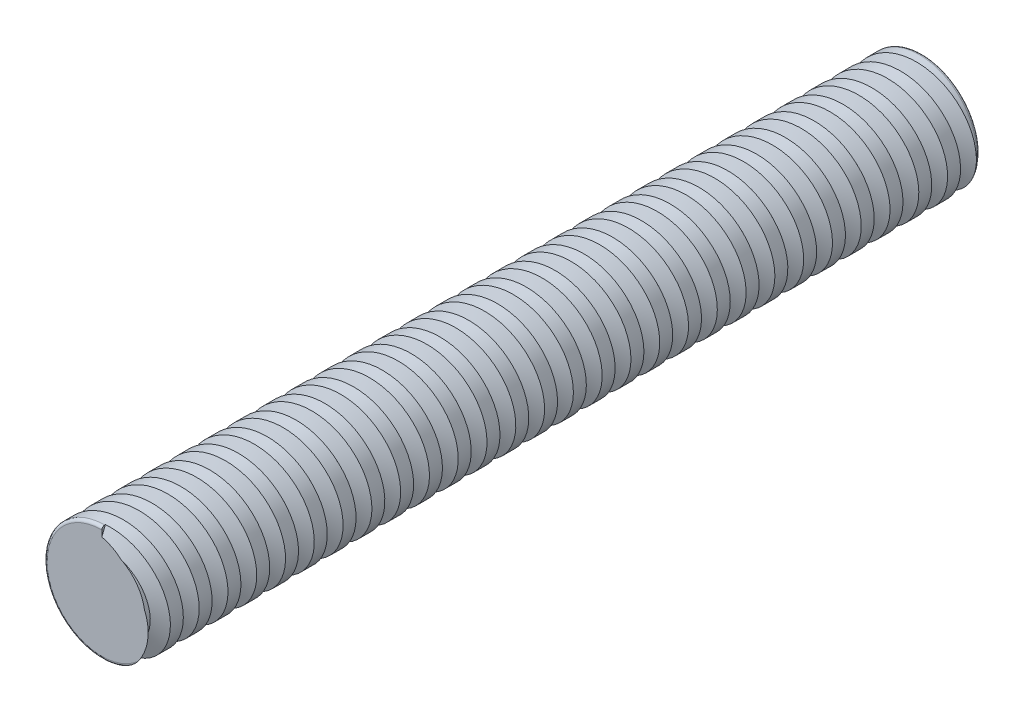
SolidWorks part; units mm, degrees
ref_plane "Front Plane" through (0, 0, 0) normal (0, 0, 1) x (1, 0, 0)
ref_plane "Top Plane" through (0, 0, 0) normal (0, 1, 0) x (1, 0, 0)
ref_plane "Right Plane" through (0, 0, 0) normal (1, 0, 0) x (0, 0, -1)
sketch "Sketch1" plane through (0, 0, 0) normal (0, 0, 1) x (1, 0, 0)
  circle A0 centre (0, 0) radius 4
  dimension "D1" = 8
extrude "Boss-Extrude1" add sketch "Sketch1" against normal blind 57
fillet "Fillet1" radius 0.2 2 edges at (4, 0, -57) (4, 0, 0)
sketch "Sketch2" plane through (0, 0, 0) normal (0, 0, 1) x (1, 0, 0)
  circle A0 centre (0, 0) radius 4
  dimension "D1" = 8
sketch "Sketch3" plane through (0, 0, 0) normal (0, 1, 0) x (1, 0, 0)
  line L0 (3, 0.35) -> (3, 0.05)
  line L1 (3, 0.05) -> (5, -0.75)
  line L2 (5, -0.75) -> (5, 1.15)
  line L3 (5, 1.15) -> (3, 0.35)
  line L4 (5, 0.2) -> (3, 0.2)
  line L7 (4, 0.2) -> (-4, 0.2) construction
  point P7 (4, 0.2)
  dimension "D1" = 1.9
  dimension "D2" = 2
  dimension "D3" = 0.3
  dimension "D4" = 4
curve "Helix/Spiral1" pitch 2 height 57 turns 28.5
sweep "Cut-Sweep1" cut profiles "Sketch3" path "Helix/Spiral1"
